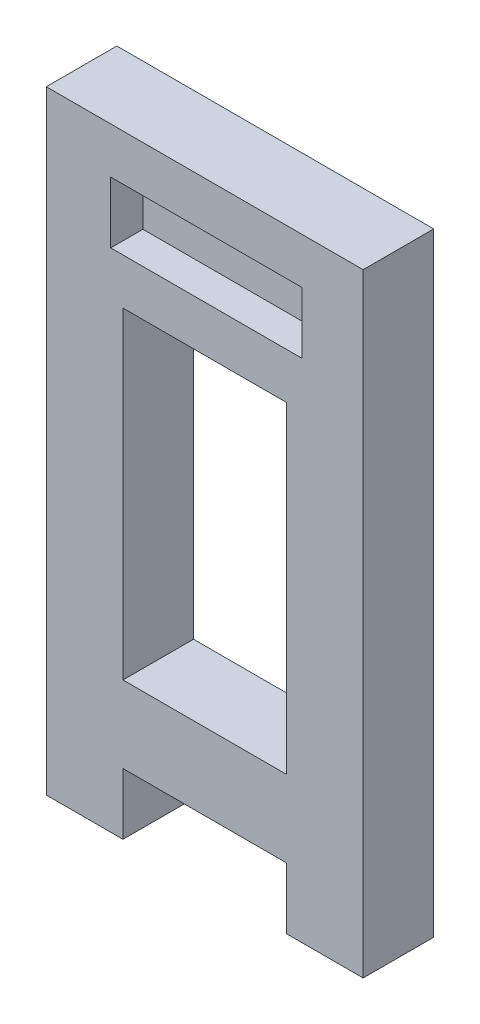
SolidWorks part; units mm, degrees
ref_plane "Front Plane" through (0, 0, 0) normal (0, 0, 1) x (1, 0, 0)
ref_plane "Top Plane" through (0, 0, 0) normal (0, 1, 0) x (1, 0, 0)
ref_plane "Right Plane" through (0, 0, 0) normal (1, 0, 0) x (0, 0, -1)
sketch "Sketch1" plane through (0, 0, 0) normal (0, 0, 1) x (1, 0, 0)
  line L0 (0, 0) -> (0, -2)
  line L1 (2.5, 0) -> (7.83, 0)
  line L2 (0, 0) -> (0, 18)
  line L3 (0, 18) -> (10.33, 18)
  line L4 (10.33, 0) -> (10.33, 18)
  line L5 (0, -2) -> (2.5, -2)
  line L6 (2.5, -2) -> (2.5, 0)
  line L7 (10.33, 0) -> (10.33, -2)
  line L8 (10.33, -2) -> (7.83, -2)
  line L9 (7.83, -2) -> (7.83, 0)
  line L12 (2.5, 2.5) -> (7.83, 2.5)
  line L13 (2.5, 2.5) -> (2.5, 13)
  line L14 (2.5, 13) -> (7.83, 13)
  line L15 (7.83, 2.5) -> (7.83, 13)
  line L16 (2.1, 14.5) -> (8.33, 14.5)
  line L17 (2.1, 14.5) -> (2.1, 16.5)
  line L18 (2.1, 16.5) -> (8.33, 16.5)
  line L19 (8.33, 14.5) -> (8.33, 16.5)
  point P19 (2.1, 15.5)
  dimension "D1" = 18
  dimension "D2" = 2
  dimension "D3" = 2.1
  dimension "D4" = 2
  dimension "D5" = 2
  dimension "D6" = 2.5
  dimension "D7" = 2.5
  dimension "D8" = 10.5
  dimension "D9" = 2
  dimension "D10" = 1.5
  dimension "D11" = 2.5
  dimension "D12" = 0.4
  dimension "D13" = 5.33
extrude "Boss-Extrude1" add sketch "Sketch1" along normal blind 2.3
extrude "Boss-Extrude2" add sketch "Sketch1<2>" along normal blind 1.25 contours L16 L19 L18 L17
sketch "Sketch1<2>" plane through (0, 0, 0) normal (0, 0, 1) x (1, 0, 0) same geometry as "Sketch1"
